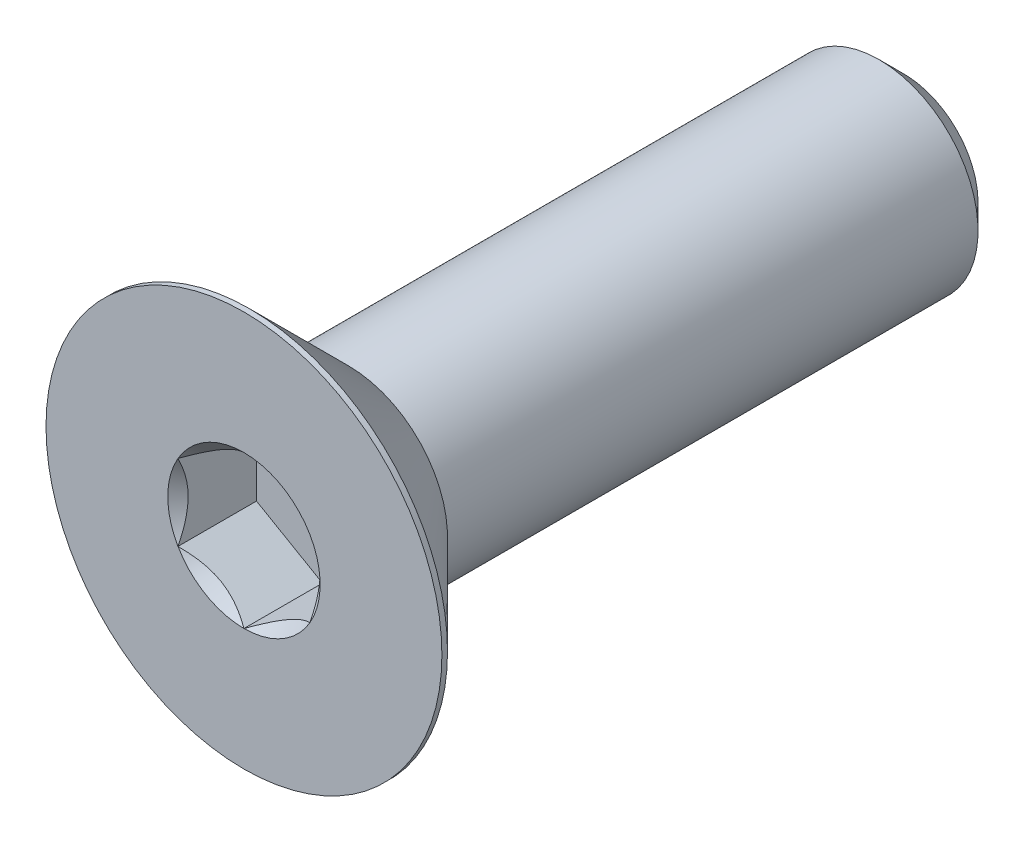
SolidWorks part; units mm, degrees
ref_plane "Front" through (0, 0, 0) normal (0, 0, 1) x (1, 0, 0)
ref_plane "Top" through (0, 0, 0) normal (0, 1, 0) x (1, 0, 0)
ref_plane "Right" through (0, 0, 0) normal (1, 0, 0) x (0, 0, -1)
sketch "Sketch11" plane through (0, 0, 0) normal (1, 0, 0) x (0, 0, -1)
  line L0 (-5, 3) -> (5, 3) construction
  line L5 (-5, 3) -> (-5, -3) construction
  line L6 (5, 1.5) -> (5, -1.5) construction
  line L7 (-4.99, 1) -> (-4.99, -1) construction
  line L8 (4.9688, 1.5541) -> (5.4688, 1.5541) construction
  line L9 (5.4688, 1.5541) -> (5.2188, 1.1211) construction
  line L10 (5.2188, 1.1211) -> (4.9688, 1.5541) construction
  line L11 (5.1875, 1.1752) -> (5.25, 1.1752) construction
  line L12 (5.2188, 1.1752) -> (5.2188, 1.1211) construction
  line L13 (4.9844, 1.5271) -> (5.4531, 1.5271) construction
  line L14 (5.2188, 1.5541) -> (5.2188, 1.5) construction
  line L15 (5, 1.5) -> (5.4375, 1.5) construction
  line L17 (-4.915, 3) -> (-1.915, 0) construction
  line L18 (-1.915, 0) -> (-4.915, -3) construction
  point P3 (-3.3, 3)
  point P8 (0, 3)
  point P21 (5.2188, 1.5271)
  point P26 (-5, 0)
  point P28 (-4.99, 0)
  point P29 (5, 0)
  dimension "Length" = 10
  dimension "Head Diameter" = 6
  dimension "Thread Major Diameter" = 3
  dimension "Head Height" = 1.7
  dimension "Drive Size" = 2
  dimension "Thread Pitch" = 0.5
  dimension "D1" = 0.0625
  dimension "D2" = 0.01
  dimension "D3" = 0.085
  dimension "Countersink Angle" = 90
sketch "Sketch1" plane through (0, 0, 0) normal (1, 0, 0) x (0, 0, -1)
  line L2 (-3.3, 1.5) -> (5, 1.5)
  line L3 (5, 1.5) -> (5, 0)
  line L4 (-3.81, 1.5) -> (-3.81, 0)
  line L5 (-3.3, 1.5) -> (-3.81, 1.5)
  line L6 (-5, 3) -> (-5, -3) construction
  line L7 (5, 1.5) -> (5, -1.5) construction
  line L8 (-3.81, 0) -> (5, 0)
  dimension "D1" = 1.19
revolve "Revolve1" add sketch "Sketch1" angle 360 mid plane about L8
cosmetic thread "Cosmetic Thread1" parameters "D1"=8.8449, "D2"=2
chamfer "Chamfer1" distance 0.375 angle 45 1 edges at (0, -1.5, -5)
sketch "Sketch7" plane through (0, 0, 0) normal (1, 0, 0) x (0, 0, -1)
  line L2 (-5, 3) -> (-4.915, 3)
  line L5 (-3.3, 1.385) -> (-3.3, 0)
  line L6 (-5, 3) -> (-5, 0)
  line L8 (-5, 3) -> (-5, -3) construction
  line L9 (-5, 0) -> (-3.3, 0)
  line L12 (-4.915, 3) -> (-3.3, 1.385)
  line L13 (-4.915, 3) -> (-1.915, 0) construction
revolve "Revolve2" add sketch "Sketch7" angle 360 mid plane about L9 region at (0, 1.1696, 4.2571)
ref_plane "Plane1" through (0, 0, 3.3) normal (0, 0, 1) x (1, 0, 0)
sketch "Sketch5" plane through (0, 0, 5) normal (0, 0, 1) x (1, 0, 0)
  line L1 (1, -0.5774) -> (1, 0.5774)
  line L2 (1, 0.5774) -> (0, 1.1547)
  line L3 (0, 1.1547) -> (-1, 0.5774)
  line L4 (-1, 0.5774) -> (-1, -0.5774)
  line L5 (-1, -0.5774) -> (0, -1.1547)
  line L6 (0, -1.1547) -> (1, -0.5774)
  circle A0 centre (0, 0) radius 1 construction
extrude "Cut-Extrude2" cut sketch "Sketch5" against normal blind 1.19
sketch "Sketch6" plane through (0, 0, 5) normal (0, 0, -1) x (-1, 0, 0)
  circle A0 centre (0, 0) radius 1.1547
extrude "Cut-Extrude3" cut sketch "Sketch6" along normal blind 1.19 draft 45
sketch "Sketch12" plane through (0, 0, -5) normal (0, 0, -1) x (-1, 0, 0)
  circle A0 centre (0, 0) radius 1.5 construction
  circle A1 centre (0, 0) radius 1.5
curve "Helix/Spiral1" [suppressed] pitch 0.5 height 10 turns 20
sketch "Sketch13" plane through (0, 0, 0) normal (1, 0, 0) x (0, 0, -1)
  line L0 (4.9844, 1.5271) -> (5.4531, 1.5271)
  line L1 (5.4531, 1.5271) -> (5.25, 1.1752)
  line L2 (5.25, 1.1752) -> (5.1875, 1.1752)
  line L3 (5.1875, 1.1752) -> (4.9844, 1.5271)
sweep "Cut-Sweep1" [suppressed] cut profiles "Sketch13" path "Helix/Spiral1"
combine bodies "Combine1" operation type add bodies to combine 113 108
equation "\"D1@Chamfer1\"=\"Thread Pitch@Sketch11\" * .75"
equation "\"D1@Cut-Extrude2\"= \"Head Height@Sketch11\" * .7"
equation "\"D1@Cut-Extrude3\" = \"D1@Cut-Extrude2\""
equation "\"D1@Sketch11\"=\"Thread Pitch@Sketch11\"/8"
equation "\"D3@Sketch11\"=\"Head Height@Sketch11\"*.05"
equation "\"D4@Helix/Spiral1\"=\"Thread Pitch@Sketch11\""
equation "\"D1@Sketch1\"=\"Head Height@Sketch11\"*.7"
equation "\"D3@Helix/Spiral1\"=\"Length@Sketch11\""
